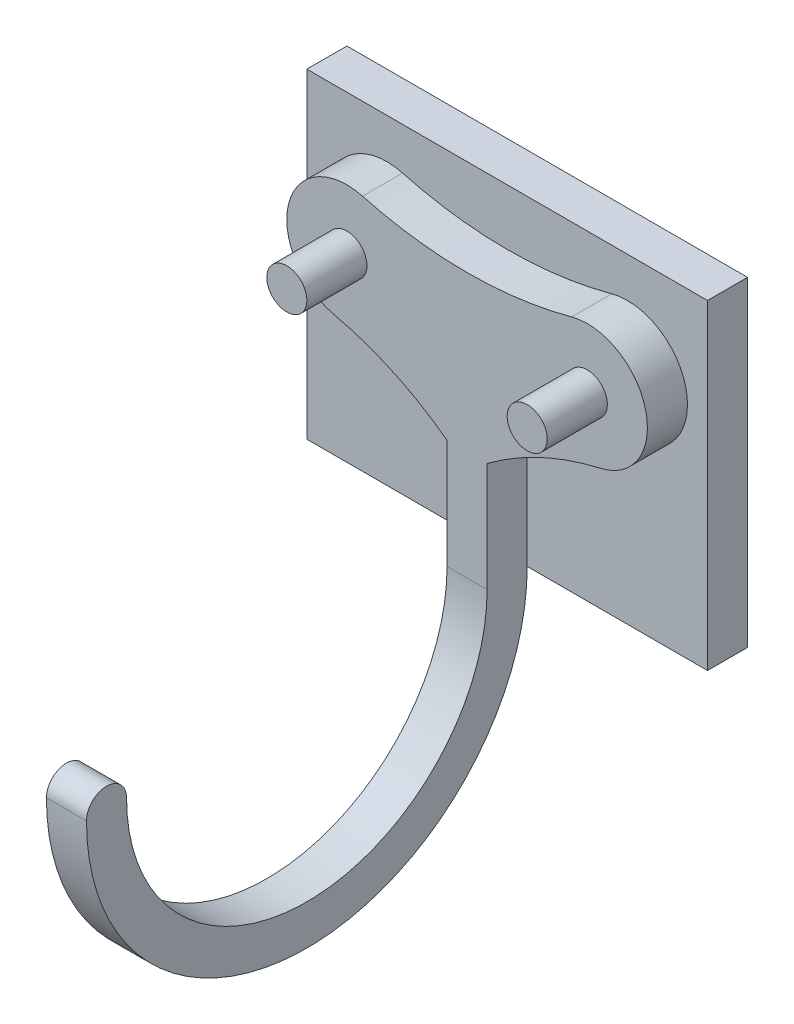
SolidWorks part; units mm, degrees
ref_plane "Front Plane" through (0, 0, 0) normal (0, 0, 1) x (1, 0, 0)
ref_plane "Top Plane" through (0, 0, 0) normal (0, 1, 0) x (1, 0, 0)
ref_plane "Right Plane" through (0, 0, 0) normal (1, 0, 0) x (0, 0, -1)
sketch "Sketch1" plane through (0, 0, 0) normal (0, 0, 1) x (1, 0, 0)
  line L0 (0, 11.6676) -> (0, -11.6676) construction
  line L1 (-10, -8) -> (10, -8)
  line L2 (-10, -8) -> (-10, 8)
  line L3 (-10, 8) -> (10, 8)
  line L4 (10, -8) -> (10, 8)
  line L5 (-10, -8) -> (10, 8) construction
  line L6 (-10, 8) -> (10, -8) construction
  line L7 (-1, -2.5499) -> (-1, -8)
  line L8 (1, -2.5499) -> (1, -8)
  circle A0 centre (-6, 3) radius 1
  arc A2 (-5.2174, 5.8961) -> (-6.6667, 0.075) centre (-6, 3) ccw
  circle A4 centre (6, 3) radius 1
  arc A5 (5.2174, 5.8961) -> (6.6667, 0.075) centre (6, 3) cw
  arc A6 (-5.2174, 5.8961) -> (5.2174, 5.8961) centre (0, 25.2036) ccw
  arc A7 (-1, -2.5499) -> (-6.6667, 0.075) centre (-10, -14.5499) ccw
  arc A8 (1, -2.5499) -> (6.6667, 0.075) centre (10, -14.5499) cw
  point P0 (0, 0)
  point P12 (0, 0)
  point P24 (-7.6391, -14.9252)
  dimension "D4" = 2
  dimension "D3" = 5
  dimension "D6" = 6
  dimension "D7" = 20
  dimension "D9" = 15
  dimension "D1" = 20
  dimension "D2" = 16
  dimension "D5" = 6
  dimension "D8" = 2
extrude "Boss-Extrude1" add sketch "Sketch1" along normal blind 2 contours A8 L8 L1 L4 L3 L2 L7 A7 A2 A6 A5 region at (-9.7439, 0, 0)
extrude "Boss-Extrude2" add sketch "Sketch1<4>" along normal blind 4 contours L8 A8 A5 A6 A2 A7 L7 L1 A0 A4 region at (0, 1.5189, 0)
sketch "Sketch1<4>" plane through (0, 0, 0) normal (0, 0, 1) x (1, 0, 0) same geometry as "Sketch1"
extrude "Boss-Extrude3" add sketch "Sketch1<6>" along normal blind 7 contours A0 | A4 region at (-6, 3, 0) region at (6, 3, 0)
sketch "Sketch1<6>" plane through (0, 0, 0) normal (0, 0, 1) x (1, 0, 0) same geometry as "Sketch1"
sketch "Sketch2" plane through (1, 0, 0) normal (1, 0, 0) x (0, 0, -1)
  line L0 (-4, -2.5499) -> (-4, -8) construction
  line L2 (-2, -8) -> (-4, -8)
  arc A0 (-4, -8) -> (-22, -8) centre (-13, -8) cw
  arc A1 (-2, -8) -> (-24, -8) centre (-13, -8) cw
  arc A2 (-24, -8) -> (-22, -8) centre (-23, -8) cw
  dimension "D1" = 9
  dimension "D2" = 2
extrude "Boss-Extrude4" add sketch "Sketch2" against normal up to surface (2 mm away) up to face at (-1, -5.275, 3)
